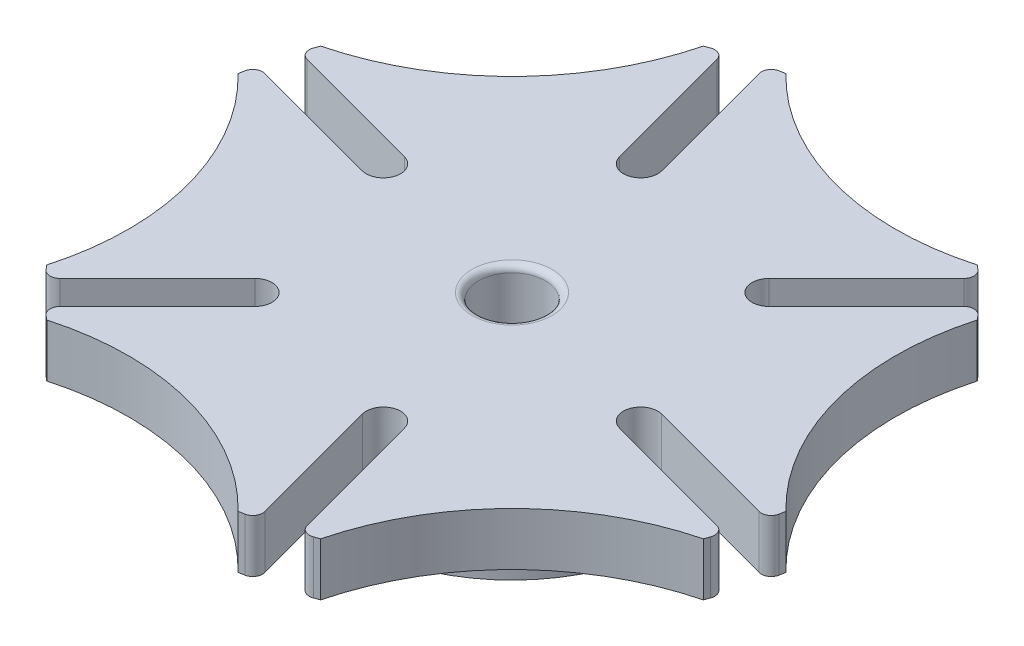
SolidWorks part; units mm, degrees
ref_plane "Front Plane" through (0, 0, 0) normal (0, 0, 1) x (1, 0, 0)
ref_plane "Top Plane" through (0, 0, 0) normal (0, 1, 0) x (1, 0, 0)
ref_plane "Right Plane" through (0, 0, 0) normal (1, 0, 0) x (0, 0, -1)
sketch "Sketch1" plane through (0, 0, 0) normal (0, 1, 0) x (1, 0, 0)
  circle A0 centre (0, 0) radius 63.5
  dimension "D1" = 127
extrude "Boss-Extrude1" add sketch "Sketch1" along normal blind 10.16
sketch "Sketch2" plane through (0, 10.16, 0) normal (0, 1, 0) x (1, 0, 0)
  line L0 (0, 0) -> (-71.842, 71.842) construction
  circle A0 centre (-71.842, 71.842) radius 50.8
  dimension "D2" = 101.6
  dimension "D1" = 101.6
extrude "Cut-Extrude1" cut sketch "Sketch2" against normal through all
pattern_circular "CirPattern1" count 6 over 360 about axis through (0, 0, 0) along (0, 1, 0) of "Cut-Extrude1"
sketch "Sketch3" plane through (0, 10.16, 0) normal (0, 1, 0) x (1, 0, 0)
  line L0 (0, 0) -> (-61.3363, 16.435) construction
  line L1 (-61.3363, 16.435) -> (-33.735, 9.0393) construction
  line L2 (-60.4817, 19.6245) -> (-32.8803, 12.2287)
  line L3 (-62.1909, 13.2455) -> (-34.5896, 5.8498)
  arc A0 (-59.3405, 22.6044) -> (-62.6925, 10.0943) centre (0, 0) ccw construction
  arc A1 (-60.4817, 19.6245) -> (-62.1909, 13.2455) centre (-61.3363, 16.435) ccw
  arc A2 (-34.5896, 5.8498) -> (-32.8803, 12.2287) centre (-33.735, 9.0393) ccw
  point P6 (-47.5356, 12.7371)
  dimension "D2" = 3.302
  dimension "D1" = 28.575
extrude "Cut-Extrude2" cut sketch "Sketch3" against normal through all
sketch "Sketch4" plane through (0, 10.16, 0) normal (0, 1, 0) x (1, 0, 0)
  circle A0 centre (0, 0) radius 6.4135
  dimension "D1" = 12.827
extrude "Cut-Extrude3" cut sketch "Sketch4" against normal through all
pattern_circular "CirPattern2" count 6 over 360 about axis through (0, 0, 0) along (0, 1, 0) of "Cut-Extrude2"
fillet "Fillet1" radius 1.905 12 edges at (-62.1079, 5.08, -13.2233) (-60.3987, 5.08, -19.6023) (-19.6023, 5.08, -60.3987) (-13.2233, 5.08, -62.1079) (42.5057, 5.08, -47.1754) (47.1754, 5.08, -42.5057) (62.1079, 5.08, 13.2233) (60.3987, 5.08, 19.6023) (19.6023, 5.08, 60.3987) (13.2233, 5.08, 62.1079) (-42.5057, 5.08, 47.1754) (-47.1754, 5.08, 42.5057)
sketch "Sketch5" plane through (0, 0, 0) normal (0, -1, 0) x (-1, 0, 0)
  circle A0 centre (0, 0) radius 31.75
  dimension "D1" = 63.5
extrude "Boss-Extrude2" add sketch "Sketch5" along normal blind 15.24
sketch "Sketch6" plane through (0, 0, 0) normal (0, 1, 0) x (1, 0, 0)
  circle A0 centre (0, 0) radius 6.4135
  circle A1 centre (0, 0) radius 6.4135 construction
extrude "Cut-Extrude4" cut sketch "Sketch6" against normal through all
fillet "Fillet2" radius 2.54 6 edges at (30.6681, 0, -8.2175) (22.4506, 0, 22.4506) (-8.2175, 0, 30.6681) (-30.6681, 0, 8.2175) (-22.4506, 0, -22.4506) (8.2175, 0, -30.6681)
fillet "Fillet3" radius 5.08 1 edges at (0, -15.24, 6.4135)
fillet "Fillet4" radius 1.27 1 edges at (0, 10.16, 6.4135)
